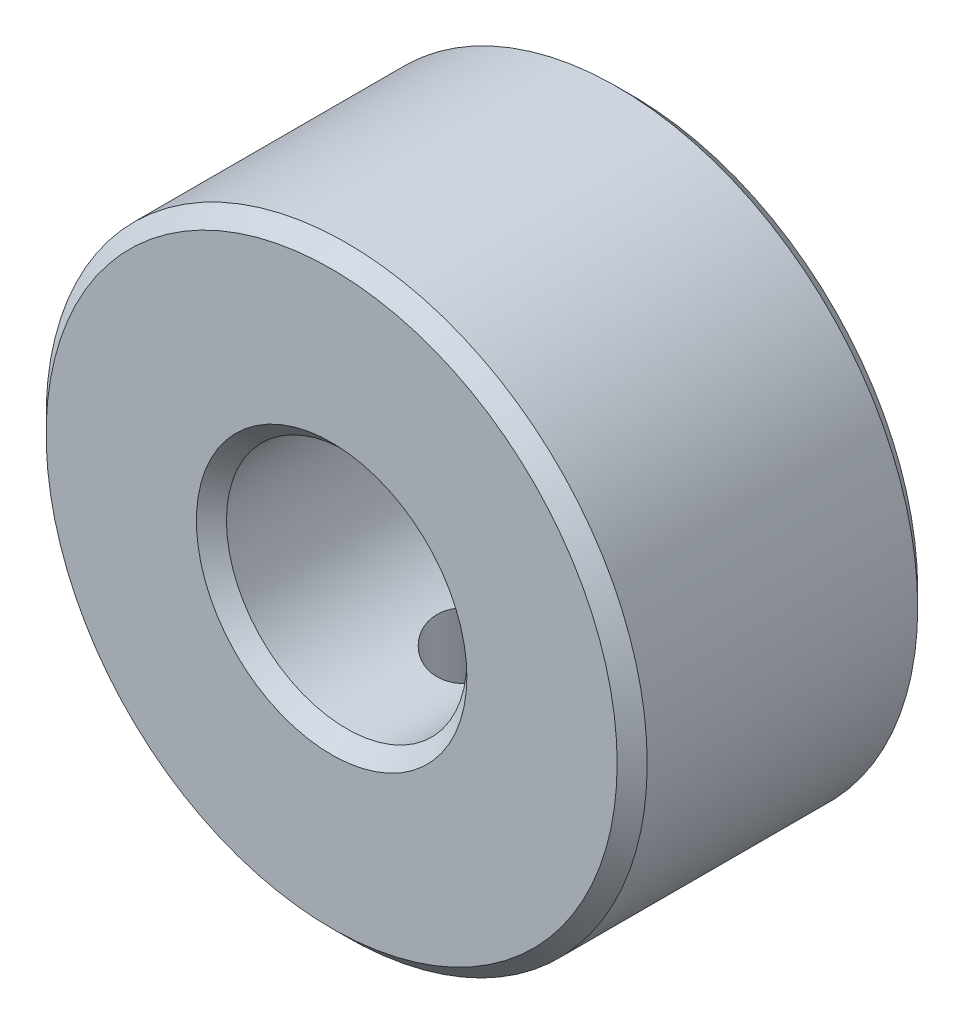
SolidWorks part; units mm, degrees
ref_plane "Front" through (0, 0, 0) normal (0, 0, 1) x (1, 0, 0)
ref_plane "Top" through (0, 0, 0) normal (0, 1, 0) x (1, 0, 0)
ref_plane "Right" through (0, 0, 0) normal (1, 0, 0) x (0, 0, -1)
sketch "Sketch1" plane through (0, 0, 0) normal (0, 0, 1) x (1, 0, 0)
  circle A0 centre (0, 0) radius 10
  circle A1 centre (0, 0) radius 4
  dimension "d" = 8
  dimension "D0" = 20
extrude "Base-Extrude" add sketch "Sketch1" against normal blind 10
chamfer "Chamfer1" distance 0.5 angle 45 2 edges at (10, 0, -10) (10, 0, 0)
sketch "Sketch2" plane through (0, 0, 0) normal (0, 1, 0) x (1, 0, 0)
  line L1 (0, 3.5505) -> (0, -10.3547) construction
  line L3 (9.5, 10) -> (-9.5, 10) construction
  circle A0 centre (0, 5) radius 1.5
  dimension "H/2" = 5
extrude "Hole" cut sketch "Sketch2" against normal through all
chamfer "Chamfer2" distance 0.5 angle 45 2 edges at (4, 0, 0) (4, 0, -10)
equation "\"H/2@Sketch2\" = \"H@Base-Extrude\" / 2"
